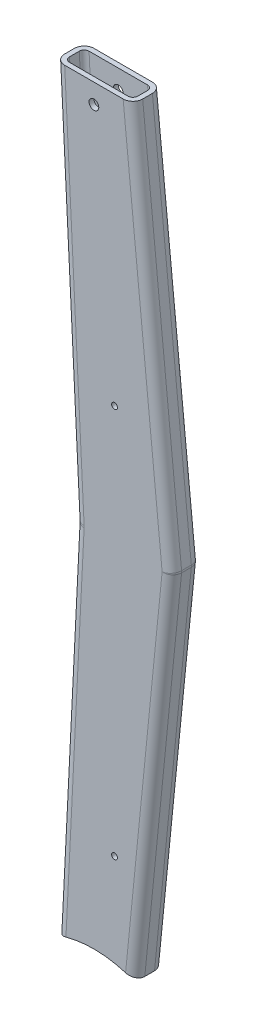
SolidWorks part; units mm, degrees
ref_plane "Front Plane" through (0, 0, 0) normal (0, 0, 1) x (1, 0, 0)
ref_plane "Top Plane" through (0, 0, 0) normal (0, 1, 0) x (1, 0, 0)
ref_plane "Right Plane" through (0, 0, 0) normal (1, 0, 0) x (0, 0, -1)
sketch "Sketch1" plane through (0, 0, 0) normal (0, 0, 1) x (1, 0, 0)
  line L0 (0, 400) -> (20, 400) construction
  line L1 (0, 0) -> (120, 0) construction
  line L2 (0, 0) -> (0, 800) construction
  line L3 (0, 800) -> (120, 800) construction
  line L4 (120, 0) -> (120, 800) construction
  line L5 (0, 0) -> (20, 400)
  line L6 (20, 400) -> (0, 800)
  line L7 (0, 800) -> (80, 800)
  line L8 (80, 800) -> (120, 400)
  line L9 (120, 400) -> (80, 0)
  line L10 (80, 0) -> (0, 0)
  dimension "D1" = 800
  dimension "D2" = 120
  dimension "D3" = 20
  dimension "D4" = 80
  dimension "D5" = 80
extrude "Extrude1" add sketch "Sketch1" along normal blind 30
sketch "Sketch2" plane through (0, 0, 0) normal (0, 0, 1) x (1, 0, 0)
  line L0 (40, 0) -> (40, -80) construction
  line L1 (0, 0) -> (80, 0) construction
  circle A0 centre (40, -80) radius 110
  dimension "D2" = 220
  dimension "D1" = 80
extrude "Extrude2" cut sketch "Sketch2" along normal through all
fillet "Fillet1" radius 10 10 edges at (120, 400, 15) (100, 600, 30) (10.5727, 211.4547, 30) (10.5727, 211.4547, 0) (20, 400, 15) (10, 600, 0) (10, 600, 30) (101.08, 210.7999, 0) (101.08, 210.7999, 30) (100, 600, 0)
shell "Shell1" thickness 5 removed face at (39.9926, 800, 15) removed face at (41.7306, 24.7076, 15.0047)
sketch "Sketch3" plane through (0, 0, 30) normal (0, 0, 1) x (1, 0, 0)
  circle A0 centre (61.1455, 122.9093) radius 3
  circle A1 centre (61.1455, 522.9093) radius 3
  dimension "D1" = 6
  dimension "D2" = 6
  dimension "D3" = 100
  dimension "D4" = 60
  dimension "D5" = 400
extrude "Extrude4" [suppressed] cut sketch "Sketch3" against normal through all
sketch "Sketch4" plane through (0, 0, 0) normal (0, 0, -1) x (-1, 0, 0)
  circle A0 centre (-61.1455, 122.9093) radius 3
  circle A1 centre (-61.1455, 522.9093) radius 3
  dimension "D2" = 6
  dimension "D4" = 6
  dimension "D1" = 100
  dimension "D3" = 60
  dimension "D5" = 400
extrude "Extrude5" cut sketch "Sketch4" against normal through all
sketch "Sketch5" plane through (0, 0, 30) normal (0, 0, 1) x (1, 0, 0)
  line L0 (69.9501, 800) -> (10.0125, 800) construction
  circle A0 centre (39.9813, 780) radius 5
  point P2 (39.9813, 800)
  dimension "D2" = 10
  dimension "D1" = 20
extrude "Extrude6" cut sketch "Sketch5" against normal through all
